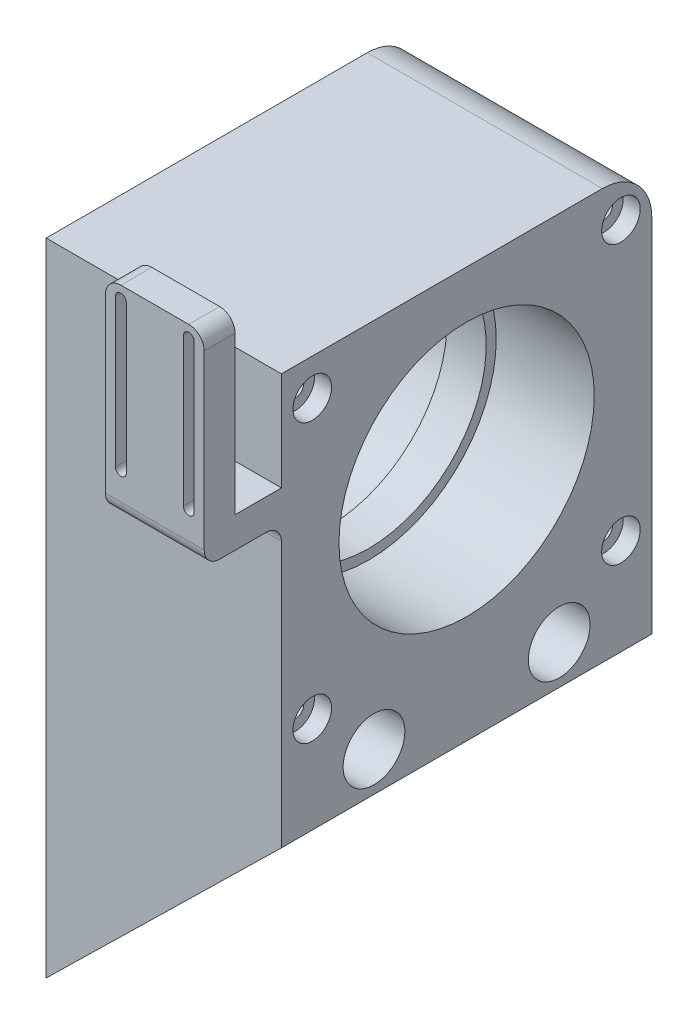
SolidWorks part; units mm, degrees
ref_plane "Front Plane" through (0, 0, 0) normal (0, 0, 1) x (1, 0, 0)
ref_plane "Top Plane" through (0, 0, 0) normal (0, 1, 0) x (1, 0, 0)
ref_plane "Right Plane" through (0, 0, 0) normal (1, 0, 0) x (0, 0, -1)
sketch "Sketch1" plane through (0, 0, 0) normal (0, 0, 1) x (1, 0, 0)
  line L0 (381, 457.2) -> (457.2, 457.2)
  line L1 (457.2, 457.2) -> (457.2, 431.8)
  line L2 (381, 457.2) -> (381, 357.2)
  line L5 (381, 357.2) -> (457.2, 431.8)
  dimension "D1" = 76.2
  dimension "D2" = 100
extrude "Boss-Extrude1" add sketch "Sketch1" along normal blind 120
sketch "Sketch3" plane through (457.2, 0, 0) normal (1, 0, 0) x (0, 0, -1)
  line L1 (-120, 431.8) -> (0, 431.8)
  line L2 (-120, 431.8) -> (-120, 357.2)
  line L3 (-120, 357.2) -> (0, 357.2)
  line L4 (0, 431.8) -> (0, 357.2)
  circle A0 centre (-90, 394.5) radius 4.25
  circle A1 centre (-30, 394.5) radius 4.25
  circle A2 centre (-90, 444.5) radius 4.25
  circle A3 centre (-30, 444.5) radius 4.25
  dimension "D1" = 30
  dimension "D2" = 30
  dimension "D3" = 37.3
  dimension "D4" = 37.3
extrude "Cut-Extrude1" cut sketch "Sketch3" against normal blind 120 contours A1 | A0
sketch "Sketch5" plane through (457.2, 0, 0) normal (1, 0, 0) x (0, 0, -1)
  circle A0 centre (-90, 394.5) radius 10
  circle A1 centre (-30, 394.5) radius 10
  circle A2 centre (-90, 444.5) radius 10
  circle A3 centre (-30, 444.5) radius 10
extrude "Cut-Extrude2" cut sketch "Sketch5" against normal blind 53
sketch "Sketch6" plane through (457.2, 0, 0) normal (1, 0, 0) x (0, 0, -1)
  circle A0 centre (-90, 444.5) radius 4.25
  circle A1 centre (-30, 444.5) radius 4.25
extrude "Cut-Extrude3" cut sketch "Sketch6" against normal blind 103
sketch "Sketch7" plane through (0, 457.2, 0) normal (0, 1, 0) x (1, 0, 0)
  line L1 (381, 0) -> (457.2, 0)
  line L2 (381, 0) -> (381, -120)
  line L3 (381, -120) -> (457.2, -120)
  line L4 (457.2, 0) -> (457.2, -120)
extrude "Boss-Extrude2" add sketch "Sketch7" along normal blind 101.6
sketch "Sketch8" plane through (381, 0, 0) normal (-1, 0, 0) x (0, 0, 1)
  line L0 (120, 457.2) -> (0, 457.2)
  line L1 (120, 558.8) -> (120, 357.2) construction
  line L2 (0, 558.8) -> (0, 357.2) construction
  line L3 (0, 558.8) -> (120, 558.8) construction
  circle A0 centre (60, 508) radius 41.35
  dimension "D1" = 101.6
  dimension "D2" = 50.8
extrude "Cut-Extrude4" cut sketch "Sketch8" against normal blind 31.75 contours A0 region at (381, 508, 60)
sketch "Sketch9" plane through (457.2, 0, 0) normal (1, 0, 0) x (0, 0, -1)
  line L0 (-120, 558.8) -> (0, 558.8) construction
  line L1 (-120, 431.8) -> (-120, 558.8) construction
  circle A0 centre (-60, 508) radius 41.35
  dimension "D1" = 50.8
  dimension "D2" = 60
extrude "Cut-Extrude5" cut sketch "Sketch9" against normal blind 31.75
sketch "Sketch10" plane through (457.2, 0, 0) normal (1, 0, 0) x (0, 0, -1)
  circle A0 centre (-60, 508) radius 38.1
extrude "Cut-Extrude6" cut sketch "Sketch10" against normal blind 76.2
sketch "Sketch13" plane through (0, 558.8, 0) normal (0, 1, 0) x (1, 0, 0)
  line L1 (381, 0) -> (457.2, 0)
  line L2 (381, 0) -> (381, -120)
  line L3 (381, -120) -> (457.2, -120)
  line L4 (457.2, 0) -> (457.2, -120)
extrude "Boss-Extrude3" add sketch "Sketch13" along normal blind 6
sketch "Sketch11" plane through (457.2, 0, 0) normal (1, 0, 0) x (0, 0, -1)
  line L0 (-120, 431.8) -> (-120, 564.8) construction
  line L1 (-110, 553) -> (-10, 553)
  line L2 (-110, 553) -> (-110, 463)
  line L3 (-110, 463) -> (-10, 463)
  line L4 (-10, 553) -> (-10, 463)
  line L5 (0, 431.8) -> (0, 564.8) construction
  circle A0 centre (-60, 508) radius 5.3331
  circle A1 centre (-110, 553) radius 2.75
  circle A2 centre (-10, 553) radius 2.75
  circle A3 centre (-10, 463) radius 2.75
  circle A4 centre (-110, 463) radius 2.75
  dimension "D1" = 10
  dimension "D2" = 10
  dimension "D3" = 45
  dimension "D4" = 90
extrude "Cut-Extrude7" cut sketch "Sketch11" against normal blind 84.4 contours L1 A1 L2 | L2 A1 L1 | L4 A2 L1 | L1 A2 L4 | L3 A3 L4 | L4 A3 L3 | L2 A4 L3 | L3 A4 L2 region at (457.2, 553.389, 110.389) region at (457.2, 551.8329, 108.8329) region at (457.2, 553.389, 9.611) region at (457.2, 551.8329, 11.1671) region at (457.2, 464.1671, 108.8329) region at (457.2, 462.611, 110.389) region at (457.2, 462.611, 9.611) region at (457.2, 464.1671, 11.1671)
sketch "Sketch12" plane through (457.2, 0, 0) normal (1, 0, 0) x (0, 0, -1)
  circle A0 centre (-110, 553) radius 6.25
  circle A1 centre (-10, 553) radius 6.25
  circle A2 centre (-10, 463) radius 6.25
  circle A3 centre (-110, 463) radius 6.25
extrude "Cut-Extrude8" cut sketch "Sketch12" against normal blind 5.5
fillet "Fillet1" radius 16 1 edges at (419.1, 564.8, 0)
sketch "Sketch17" plane through (0, 0, 120) normal (0, 0, 1) x (1, 0, 0)
  line L5 (428.45, 592.8) -> (428.45, 568.8)
  line L6 (457.2, 564.8) -> (425.2, 564.8)
  line L7 (457.2, 564.8) -> (457.2, 596.8)
  line L8 (457.2, 596.8) -> (425.2, 596.8)
  line L9 (425.2, 564.8) -> (425.2, 596.8)
  line L10 (431.95, 568.8) -> (431.95, 592.8)
  line L11 (450.45, 592.8) -> (450.45, 568.8)
  line L12 (453.95, 592.8) -> (453.95, 568.8)
  circle A4 centre (430.2, 592.8) radius 1.75
  circle A6 centre (430.2, 568.8) radius 1.75
  circle A7 centre (452.2, 568.8) radius 1.75
  circle A8 centre (452.2, 592.8) radius 1.75
  dimension "D3" = 22
  dimension "D1" = 32
  dimension "D2" = 32
  dimension "D4" = 22
  dimension "D5" = 5
  dimension "D6" = 5
  dimension "D7" = 4
  dimension "D8" = 4
  dimension "D9" = 4
  dimension "D10" = 4
sketch "Sketch18" plane through (0, 0, 120) normal (0, 0, 1) x (1, 0, 0)
  line L0 (457.2, 431.8) -> (457.2, 564.8) construction
  line L1 (457.2, 522.8) -> (425.2, 522.8)
  line L2 (457.2, 522.8) -> (457.2, 532.8)
  line L3 (457.2, 532.8) -> (425.2, 532.8)
  line L4 (425.2, 522.8) -> (425.2, 532.8)
  line L6 (381, 564.8) -> (457.2, 564.8) construction
  dimension "D1" = 32
  dimension "D2" = 32
  dimension "D3" = 10
extrude "Boss-Extrude6" add sketch "Sketch18" along normal blind 15
sketch "Sketch20" plane through (0, 0, 135) normal (0, 0, 1) x (1, 0, 0)
  line L0 (431.95, 584.6825) -> (431.95, 536.8)
  line L2 (425.2, 532.8) -> (425.2, 588.6825)
  line L3 (425.2, 588.6825) -> (457.2, 588.6825)
  line L4 (457.2, 536.6825) -> (457.2, 588.6825)
  line L5 (428.45, 584.6825) -> (428.45, 536.8)
  line L6 (450.45, 584.6825) -> (450.45, 536.8)
  line L7 (450.45, 584.6825) -> (450.45, 536.8)
  line L8 (425.2, 532.8) -> (425.2, 522.8)
  line L9 (425.2, 522.8) -> (457.2, 522.8)
  line L10 (457.2, 522.8) -> (457.2, 536.6825)
  line L11 (453.95, 584.6825) -> (453.95, 536.8)
  circle A0 centre (430.2, 584.6825) radius 1.75
  circle A1 centre (452.2, 584.6825) radius 1.75
  circle A2 centre (452.2, 536.8) radius 1.75
  circle A3 centre (430.2, 536.8) radius 1.75
  point P20 (428.45, 536.8)
  line M6 (457.2, 522.8) -> (457.2, 532.8)
  line M7 (457.2, 532.8) -> (425.2, 532.8)
  line M8 (425.2, 532.8) -> (425.2, 522.8)
  line M9 (425.2, 522.8) -> (457.2, 522.8)
  dimension "D1" = 22
  dimension "D2" = 22
  dimension "D3" = 5
  dimension "D4" = 52
  dimension "D5" = 4
  dimension "D6" = 5
  dimension "D7" = 4
extrude "Boss-Extrude7" add sketch "Sketch20" along normal blind 10 contours L4 L3 L2 A3 L5 A0 L0 A2 L6 A1 L7 M7 | M9 M6 M7 M8 region at (441.2, 527.8, 135) region at (441.2, 560.7413, 135)
fillet "Fillet3" radius 5 4 edges at (441.2, 522.8, 145) (425.2, 588.6825, 140) (457.2, 588.6825, 140) (441.2, 522.8, 120)
